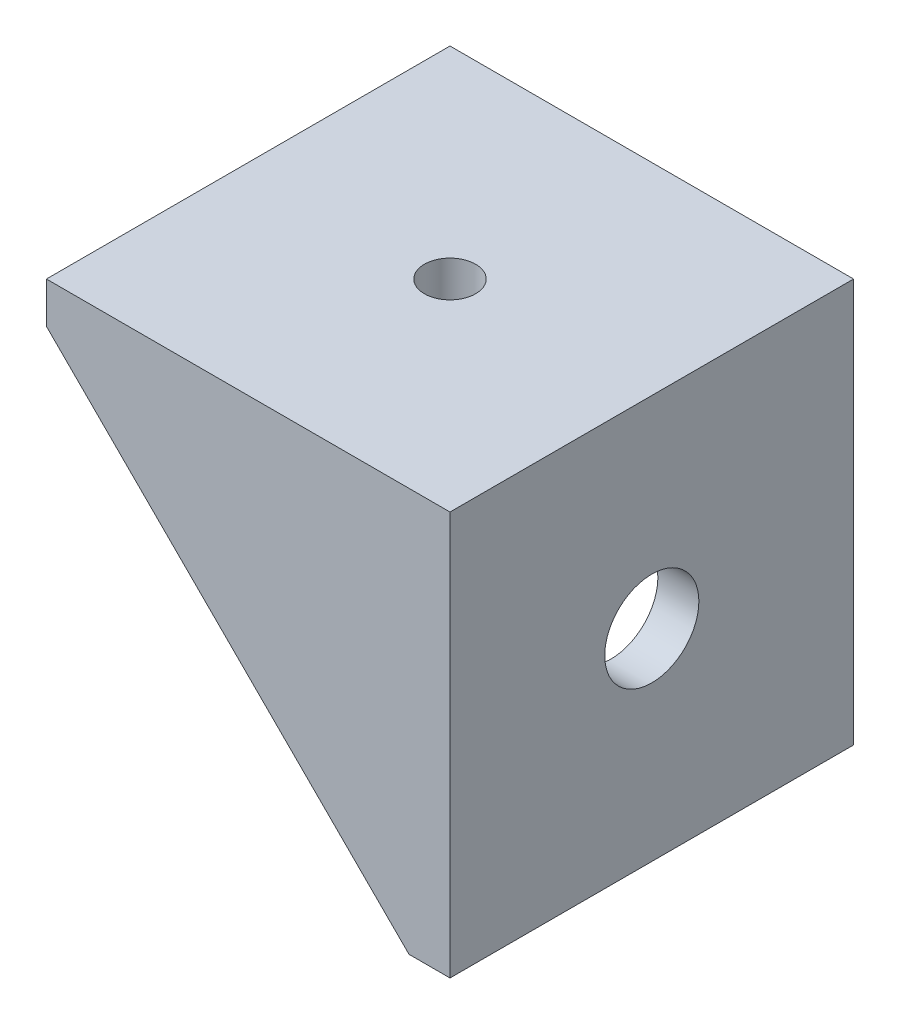
SolidWorks part; units mm, degrees
ref_plane "Front Plane" through (0, 0, 0) normal (0, 0, 1) x (1, 0, 0)
ref_plane "Top Plane" through (0, 0, 0) normal (0, 1, 0) x (1, 0, 0)
ref_plane "Right Plane" through (0, 0, 0) normal (1, 0, 0) x (0, 0, -1)
sketch "Sketch1" plane through (0, 0, 0) normal (0, 0, 1) x (1, 0, 0)
  line L0 (0, 0) -> (-30, 0)
  line L1 (-30, 0) -> (-30, -3.048)
  line L2 (-30, -3.048) -> (-3.048, -3.048)
  line L3 (-3.048, -3.048) -> (-3.048, -30)
  line L4 (-3.048, -30) -> (0, -30)
  line L5 (0, -30) -> (0, 0)
  line L6 (-3.048, -30) -> (-30, -3.048)
  dimension "D1" = 30
  dimension "D2" = 3.048
extrude "Boss-Extrude1" add sketch "Sketch1" along normal mid plane 30 contours L4 L5 L0 L1 L2 L3 region at (-0.4243, -15, 0)
extrude "Boss-Extrude2" add sketch "Sketch1<3>" against normal blind 3.048 from surface contours L6 L3 L2 region at (-12.032, -12.032, 0) starting at face at (-11.016, -11.016, 15)
sketch "Sketch1<3>" plane through (0, 0, 0) normal (0, 0, 1) x (1, 0, 0) same geometry as "Sketch1"
extrude "Boss-Extrude3" add sketch "Sketch1<4>" along normal blind 3.048 from surface contours L6 L3 L2 region at (-12.032, -12.032, 0) starting at face at (-11.016, -11.016, -15)
sketch "Sketch1<4>" plane through (0, 0, 0) normal (0, 0, 1) x (1, 0, 0) same geometry as "Sketch1"
sketch "Sketch2" plane through (0, 0, 0) normal (0, 1, 0) x (1, 0, 0)
  line L0 (-15, 15) -> (-15, -15) construction
  line L1 (0, 15) -> (-30, 15) construction
  line L2 (0, -15) -> (-30, -15) construction
  circle A0 centre (-15, 0) radius 1.905
  dimension "D1" = 3.81
extrude "Cut-Extrude1" cut sketch "Sketch2" against normal through all
sketch "Sketch3" plane through (0, 0, 0) normal (1, 0, 0) x (0, 0, -1)
  line L0 (-15, -15) -> (15, -15) construction
  line L1 (-15, -30) -> (-15, 0) construction
  line L2 (15, -30) -> (15, 0) construction
  circle A0 centre (0, -15) radius 3.5
  dimension "D1" = 7
extrude "Cut-Extrude2" cut sketch "Sketch3" against normal through all
